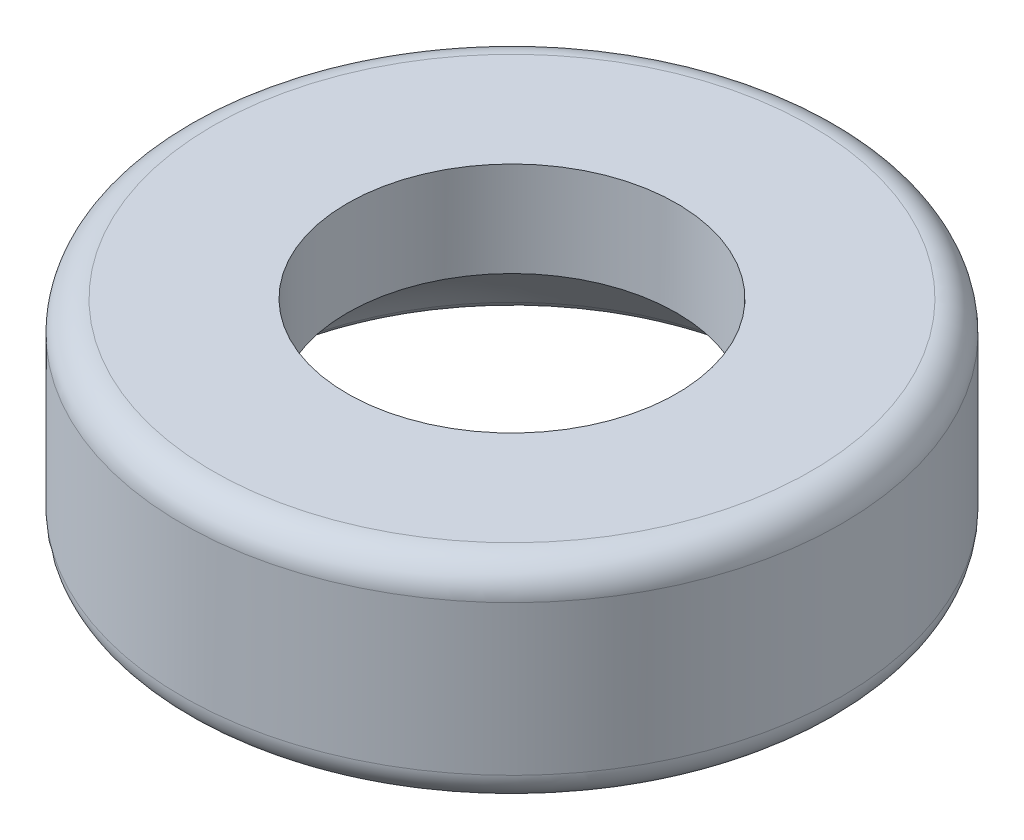
SolidWorks part; units mm, degrees
material "Nylon 101"
ref_plane "Front Plane" through (0, 0, 0) normal (0, 0, 1) x (1, 0, 0)
ref_plane "Top Plane" through (0, 0, 0) normal (0, 1, 0) x (1, 0, 0)
ref_plane "Right Plane" through (0, 0, 0) normal (1, 0, 0) x (0, 0, -1)
sketch "Sketch1" plane through (0, 0, 0) normal (0, 0, 1) x (1, 0, 0)
  line L0 (-90.9284, 0) -> (4455.4897, 0) construction
  line L1 (0, -90.9284) -> (0, 4455.4897) construction
  line L2 (4.1275, 0) -> (4.1275, 4.7625)
  line L3 (4.1275, 4.7625) -> (0, 4.7625)
  line L4 (0, 4.7625) -> (0, 4.1275)
  arc A0 (0, 4.1275) -> (4.1275, 0) centre (0, 0) cw
  dimension "D4" = 4.1275
  dimension "D1" = 4.7625
  dimension "D2" = 4.1275
  dimension "D3" = 0.635
revolve "Revolve1" add sketch "Sketch1" angle 360 about L1
fillet "Fillet1" radius 0.381 2 edges at (4.1275, 0, 0) (4.1275, 4.7625, 0)
sketch "Sketch2" plane through (0, 4.7625, 0) normal (0, 1, 0) x (1, 0, 0)
  circle A0 centre (0, 0) radius 2.0638
  dimension "D1" = 4.1275
extrude "Cut-Extrude1" cut sketch "Sketch2" against normal through all
